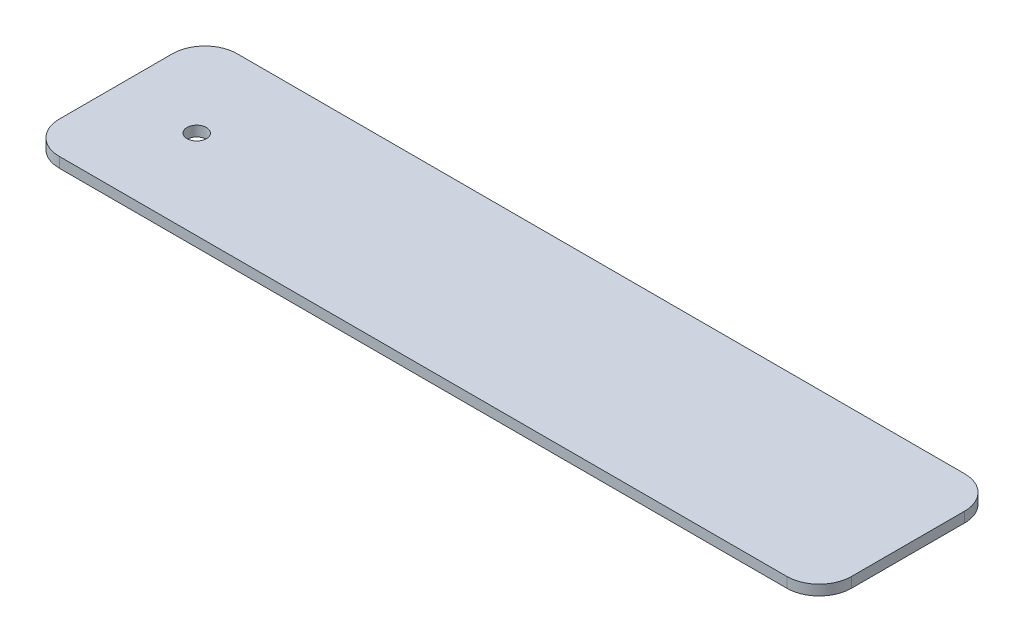
SolidWorks part; units mm, degrees
ref_plane "Front Plane" through (0, 0, 0) normal (0, 0, 1) x (1, 0, 0)
ref_plane "Top Plane" through (0, 0, 0) normal (0, 1, 0) x (1, 0, 0)
ref_plane "Right Plane" through (0, 0, 0) normal (1, 0, 0) x (0, 0, -1)
sketch "Sketch1" plane through (0, 0, 0) normal (0, 1, 0) x (1, 0, 0)
  line L0 (-25, 0) -> (0, 0) construction
  line L1 (-25, 27.5) -> (220, 27.5)
  line L2 (-25, 27.5) -> (-25, -27.5)
  line L3 (-25, -27.5) -> (220, -27.5)
  line L4 (220, 27.5) -> (220, -27.5)
  point P7 (200, 0)
  dimension "D1" = 55
  dimension "D2" = 200
  dimension "D3" = 20
  dimension "D4" = 25
extrude "Boss-Extrude1" add sketch "Sketch1" along normal blind 3.175
fillet "Fillet1" radius 10 4 edges at (-25, 1.5875, 27.5) (-25, 1.5875, -27.5) (220, 1.5875, -27.5) (220, 1.5875, 27.5)
hole_wizard "Ø6.0mm Dowel Hole1" positions "Sketch3" profile "Sketch4" hole size "Ø6.0" standard "DIN" end condition up to next
sketch "Sketch3" plane through (0, 3.175, 0) normal (0, 1, 0) x (1, 0, 0)
  point P0 (0, 0)
sketch "Sketch4" plane through (0, 3.175, 0) normal (1, 0, 0) x (0, 0, 1)
  line L0 (0, 0) -> (0, 3.175)
  line L1 (0, 3.175) -> (3, 3.175)
  line L2 (3, 3.175) -> (3, 0)
  line L5 (3, 0) -> (0, 0)
  line L11 (0, -6.35) -> (0, 107.95) construction
  dimension "Thru Hole Dia." = 6
  dimension "Thru Hole Depth" = 3.175
equation "\"Pivot to Pivot Distance\"= 200mm"
equation "\"D2@Sketch1\"=\"Pivot to Pivot Distance\""
equation "\"Plate Thickness\"= 0.125in"
equation "\"D1@Boss-Extrude1\"=\"Plate Thickness\""
